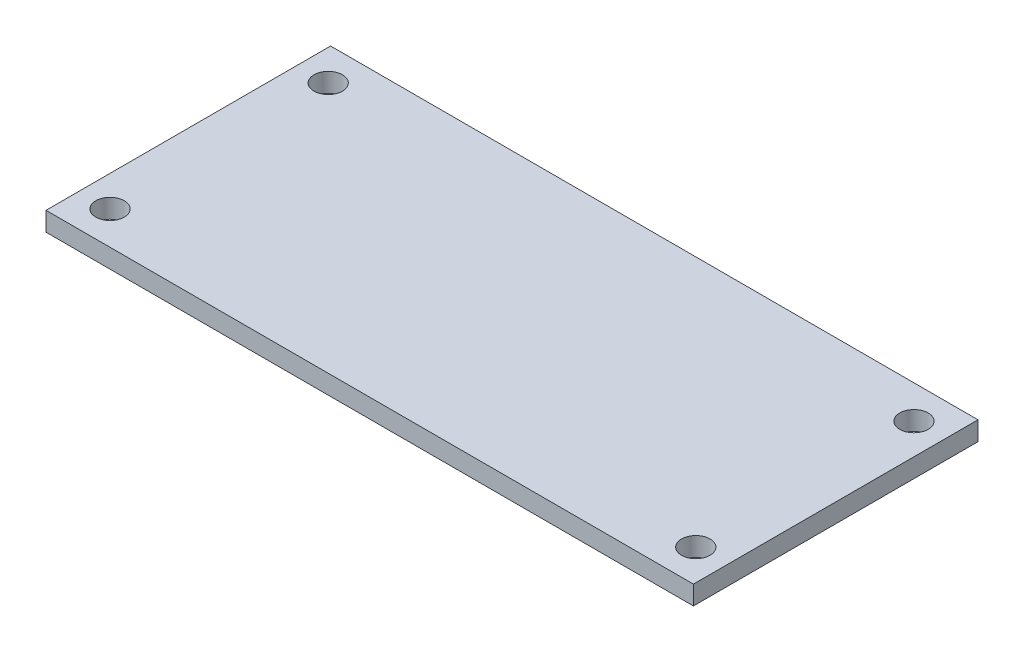
SolidWorks part; units mm, degrees
ref_plane "Front Plane" through (0, 0, 0) normal (0, 0, 1) x (1, 0, 0)
ref_plane "Top Plane" through (0, 0, 0) normal (0, 1, 0) x (1, 0, 0)
ref_plane "Right Plane" through (0, 0, 0) normal (1, 0, 0) x (0, 0, -1)
sketch "Sketch1" plane through (0, 0, 0) normal (0, 1, 0) x (1, 0, 0)
  line L1 (0, 0) -> (68.25, 0)
  line L2 (0, 0) -> (0, 30)
  line L3 (0, 30) -> (68.25, 30)
  line L4 (68.25, 0) -> (68.25, 30)
  line L8 (34.125, 26.5) -> (34.125, 30) construction
  line L9 (3.25, 26.5) -> (65, 26.5) construction
  line L10 (3.25, 26.5) -> (3.25, 3.5) construction
  line L11 (3.25, 3.5) -> (65, 3.5) construction
  line L12 (65, 26.5) -> (65, 3.5) construction
  line L14 (34.125, 3.5) -> (34.125, 0) construction
  line L16 (65, 15) -> (68.25, 15) construction
  line L18 (3.25, 15) -> (0, 15) construction
  circle A4 centre (3.25, 26.5) radius 1.5
  circle A5 centre (65, 3.5) radius 1.5
  circle A6 centre (65, 26.5) radius 1.5
  circle A7 centre (3.25, 3.5) radius 1.5
  dimension "D4" = 23
  dimension "D1" = 3
  dimension "D2" = 61.75
  dimension "D3" = 68.25
  dimension "D5" = 30
extrude "Boss-Extrude1" add sketch "Sketch1" along normal blind 2 contours L1 L4 L3 L2 A7 A6 A5 A4 region at (34.125, 0, -15)
